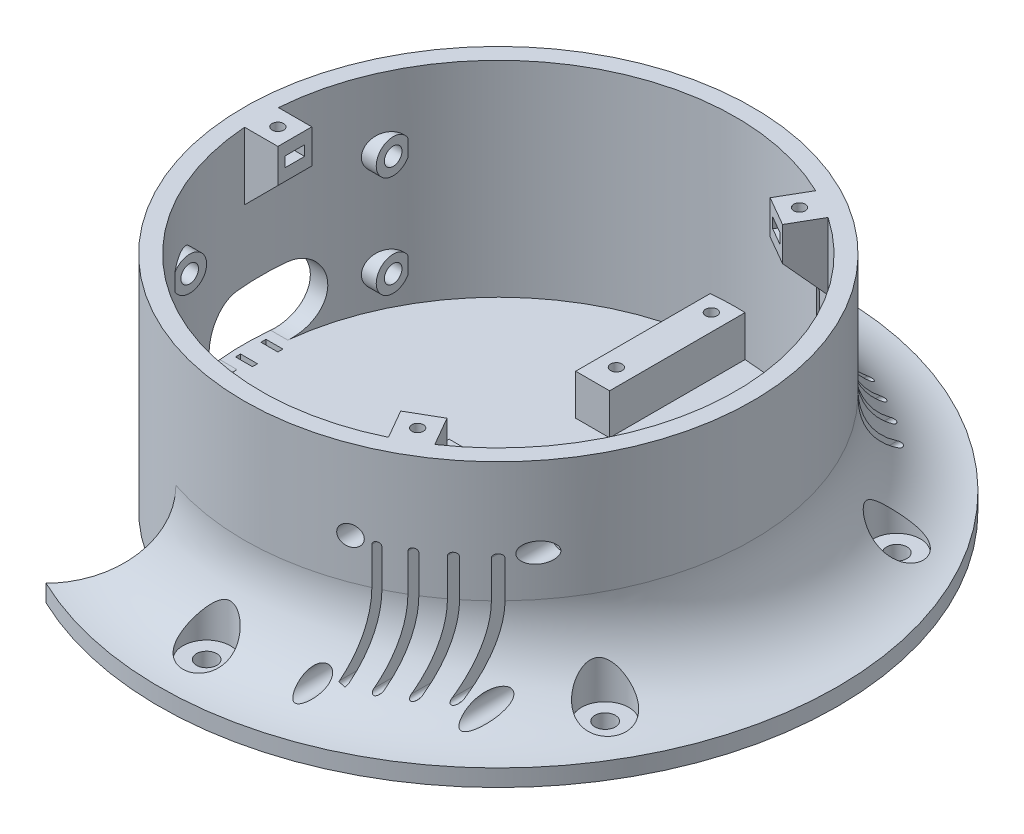
SolidWorks part; units mm, degrees
material "PLA"
ref_plane "Alzado" through (0, 0, 0) normal (0, 0, 1) x (1, 0, 0)
ref_plane "Planta" through (0, 0, 0) normal (0, 1, 0) x (1, 0, 0)
ref_plane "Vista lateral" through (0, 0, 0) normal (1, 0, 0) x (0, 0, -1)
sketch "Croquis1" plane through (0, 0, 0) normal (0, 0, 1) x (1, 0, 0)
  line L0 (0, 5) -> (0, 0)
  line L1 (0, 0) -> (100, 0)
  line L2 (100, 0) -> (100, 5)
  line L5 (75, 65.5) -> (70, 65.5)
  line L6 (70, 65.5) -> (70, 5)
  line L7 (70, 5) -> (0, 5)
  line L8 (0, 78.0387) -> (0, -48.9412) construction
  line L9 (75, 65.5) -> (75, 30)
  arc A0 (75, 30) -> (100, 5) centre (100, 30) ccw
  point P11 (100, 2.5)
  dimension "D6" = 50
  dimension "D1" = 65.5
  dimension "D2" = 70
  dimension "D3" = 75
  dimension "D4" = 100
  dimension "D5" = 5
  dimension "D7" = 5
  dimension "D8" = 35.5
revolve "Revolución1" add sketch "Croquis1" angle 360 about L8
sketch "Croquis2" plane through (0, 65.5, 0) normal (0, 1, 0) x (1, 0, 0)
  line L0 (-112.9437, 100) -> (-112.9437, -100)
  line L1 (-112.9437, 100) -> (-52.9437, 100)
  line L2 (-52.9437, 100) -> (-24, 71.0563)
  line L3 (-112.9437, -100) -> (-52.9437, -100)
  line L4 (-52.9437, -100) -> (-24, -71.0563)
  arc A0 (-24, 71.0563) -> (-24, -71.0563) centre (0, 0) ccw
  circle A1 centre (0, 0) radius 75 construction
  point P5 (-112.9437, 0)
  dimension "D1" = 200
  dimension "D2" = 60
  dimension "D3" = 135
  dimension "D4" = 24
extrude "Cortar-Extruir1" cut sketch "Croquis2" against normal blind 109
sketch "Croquis3" plane through (0, 0, 0) normal (0, 0, 1) x (1, 0, 0)
  line L0 (-72, 65.5) -> (-72, 43.5)
  line L2 (-72, 43.5) -> (-60, 55.5)
  line L3 (-60, 55.5) -> (-60, 65.5)
  line L4 (75, 65.5) -> (-75, 65.5) construction
  line L6 (-60, 65.5) -> (-70, 65.5)
  line L7 (-70, 65.5) -> (-72, 65.5)
  dimension "D1" = 10
  dimension "D2" = 45
  dimension "D3" = 10
  dimension "D4" = 2
  dimension "D5" = 70
extrude "Saliente-Extruir1" add sketch "Croquis3" along normal blind 5 and the other way blind 5
sketch "Croquis4" plane through (0, 65.5, 0) normal (0, 1, 0) x (1, 0, 0)
  line L0 (-60, 5) -> (-60, -5) construction
  circle A0 centre (-65, 0) radius 1.7
  point P6 (-60, 0)
  dimension "D2" = 3.4
  dimension "D1" = 5
extrude "Cortar-Extruir2" cut sketch "Croquis4" against normal blind 22
ref_plane "Plano1" through (0, 60.5, 0) normal (0, 1, 0) x (1, 0, 0)
sketch "Croquis5" plane through (0, 60.5, 0) normal (0, 1, 0) x (1, 0, 0)
  line L0 (-63.325, 2.9012) -> (-56.675, 2.9012)
  line L1 (-68.35, 0) -> (-66.675, -2.9012)
  line L2 (-66.675, -2.9012) -> (-63.325, -2.9012)
  line L5 (-63.325, 2.9012) -> (-66.675, 2.9012)
  line L6 (-66.675, 2.9012) -> (-68.35, 0)
  line L7 (-56.675, 2.9012) -> (-56.675, -2.9012)
  line L8 (-56.675, -2.9012) -> (-63.325, -2.9012)
  line L9 (-60, 5) -> (-69.8212, 5) construction
  line L10 (-61.65, 0) -> (-63.325, 2.9012) [skipped]
  line L11 (-62.4528, -1.3904) -> (-61.65, 0) [skipped]
  circle A0 centre (-65, 0) radius 3.35 construction
  dimension "D1" = 6.7
  dimension "D2" = 10
extrude "Cortar-Extruir3" cut sketch "Croquis5" against normal blind 1.5 and the other way blind 1.5
pattern_circular "MatrizC1" count 3 over 360 about axis through (0, 65.5, 0) along (0, 1, 0) of "Saliente-Extruir1", "Cortar-Extruir2", "Cortar-Extruir3"
sketch "Croquis6" plane through (0, 0, 0) normal (0, -1, 0) x (1, 0, 0)
  circle A0 centre (0, -86) radius 3
  dimension "D1" = 6
  dimension "D2" = 86
extrude "Cortar-Extruir4" cut sketch "Croquis6" against normal blind 30.35
ref_plane "Plano2" through (0, 20, 0) normal (0, -1, 0) x (-1, 0, 0)
sketch "Croquis7" plane through (0, 20, 0) normal (0, -1, 0) x (-1, 0, 0)
  circle A0 centre (0, 86) radius 7
  dimension "D1" = 14
extrude "Cortar-Extruir5" cut sketch "Croquis7" along normal blind 15
pattern_circular "MatrizC2" count 6 over 360 of "Cortar-Extruir4", "Cortar-Extruir5"
sketch "Croquis8" plane through (0, 0, 0) normal (0, -1, 0) x (1, 0, 0)
  line L1 (24.5, -15.5) -> (55.5, -15.5) construction
  line L2 (24.5, -15.5) -> (24.5, 15.5) construction
  line L3 (24.5, 15.5) -> (55.5, 15.5) construction
  line L4 (55.5, -15.5) -> (55.5, 15.5) construction
  circle A0 centre (24.5, 15.5) radius 1.7
  circle A1 centre (55.5, 15.5) radius 1.7
  circle A2 centre (24.5, -15.5) radius 1.7
  circle A3 centre (55.5, -15.5) radius 1.7
  point P4 (24.5, 0)
  dimension "D4" = 3.4
  dimension "D1" = 31
  dimension "D2" = 31
  dimension "D3" = 24.5
extrude "Cortar-Extruir6" cut sketch "Croquis8" against normal blind 15
sketch "Croquis9" plane through (0, 0, 0) normal (0, -1, 0) x (1, 0, 0)
  circle A0 centre (24.5, 15.5) radius 2.95
  circle A1 centre (24.5, -15.5) radius 2.95
  circle A2 centre (55.5, -15.5) radius 2.95
  circle A3 centre (55.5, 15.5) radius 2.95
  dimension "D1" = 5.9
extrude "Cortar-Extruir7" cut sketch "Croquis9" against normal blind 2.5
sketch "Croquis10" plane through (0, 5, 0) normal (0, 1, 0) x (1, 0, 0)
  line L1 (2.8, 30) -> (-7.2, 30)
  line L2 (2.8, 30) -> (2.8, 69.944)
  line L4 (-7.2, 30) -> (-7.2, 69.6287)
  arc A0 (2.8, 69.944) -> (-7.2, 69.6287) centre (0, 0) ccw
  circle A1 centre (0, 0) radius 70 construction
  dimension "D1" = 30
  dimension "D2" = 2.8
  dimension "D3" = 10
extrude "Saliente-Extruir2" add sketch "Croquis10" along normal blind 12
sketch "Croquis11" plane through (0, 17, 0) normal (0, 1, 0) x (1, 0, 0)
  circle A0 centre (-2.2, 37) radius 1.7
  dimension "D3" = 3.4
  dimension "D1" = 5
  dimension "D2" = 7
extrude "Cortar-Extruir8" cut sketch "Croquis11" against normal blind 21
ref_plane "Plano3" through (0, 10.65, 0) normal (0, 1, 0) x (1, 0, 0)
sketch "Croquis12" plane through (0, 10.65, 0) normal (0, 1, 0) x (1, 0, 0)
  line L0 (-3.875, 39.9012) -> (-10.525, 39.9012)
  line L2 (-3.875, 34.0988) -> (-0.525, 34.0988)
  line L3 (-0.525, 34.0988) -> (1.15, 37)
  line L4 (1.15, 37) -> (-0.525, 39.9012)
  line L5 (-0.525, 39.9012) -> (-3.875, 39.9012)
  line L7 (-10.525, 39.9012) -> (-10.525, 34.0988)
  line L8 (-10.525, 34.0988) -> (-3.875, 34.0988)
  line L9 (-7.2, 30) -> (2.8, 30) construction
  line L10 (-5.55, 37) -> (-3.875, 34.0988) [skipped]
  line L11 (-3.875, 39.9012) -> (-5.55, 37) [skipped]
  line L12 (-7.2, 30) -> (2.8, 30) construction
  circle A0 centre (-2.2, 37) radius 3.35 construction
  dimension "D1" = 6.7
  dimension "D2" = 10
extrude "Cortar-Extruir9" cut sketch "Croquis12" against normal blind 3
pattern_linear "MatrizL1" count 2 spacing 28 along (0, 0, -1) of "Cortar-Extruir8", "Cortar-Extruir9"
sketch "Croquis13" plane through (0, 5, 0) normal (0, 1, 0) x (1, 0, 0)
  line L1 (63.5, -36) -> (21.5, -36)
  line L2 (63.5, -36) -> (63.5, -26)
  line L3 (63.5, -26) -> (21.5, -26)
  line L4 (21.5, -36) -> (21.5, -26)
  dimension "D1" = 10
  dimension "D2" = 42
  dimension "D3" = 36
  dimension "D4" = 21.5
extrude "Cortar-Extruir10" cut sketch "Croquis13" along normal blind 42
sketch "Croquis14" plane through (0, 5, 0) normal (0, 1, 0) x (1, 0, 0)
  line L0 (60.0333, -36) -> (21.5, -36)
  line L1 (21.5, -36) -> (21.5, -66.6164)
  circle A0 centre (0, 0) radius 70
  arc A1 (39.2407, -57.9669) -> (39.2407, 57.9669) centre (0, 0) ccw construction
  arc A2 (-7.2, 69.6287) -> (60.0333, -36) centre (0, 0) ccw construction
  arc M4 (-7.2, 69.6287) -> (60.0333, -36) centre (0, 0) ccw
  dimension "D1" = 42
extrude "Saliente-Extruir3" add sketch "Croquis14" along normal blind 42 contours L0 L1 M4 region at (35.8526, 5, 47.5073)
sketch "Croquis15" plane through (0, 0, 36) normal (0, 0, -1) x (-1, 0, 0)
  line L0 (-53, 41) -> (-53, 11) construction
  line L1 (-32, 11) -> (-53, 11) construction
  line L2 (-32, 11) -> (-32, 41) construction
  line L3 (-32, 41) -> (-53, 41) construction
  line L4 (-53, 11) -> (-53, 41) construction
  line L5 (-32, 11) -> (-53, 41) construction
  line L6 (-32, 41) -> (-53, 11) construction
  line L7 (-52, 41) -> (-52, 11)
  line L8 (-54, 41) -> (-54, 11)
  line L9 (-32, 41) -> (-32, 11) construction
  line L10 (-31, 41) -> (-31, 11)
  line L11 (-33, 41) -> (-33, 11)
  line L12 (-46, 41) -> (-46, 11) construction
  line L13 (-45, 41) -> (-45, 11)
  line L14 (-47, 41) -> (-47, 11)
  line L15 (-39, 41) -> (-39, 11) construction
  line L16 (-38, 41) -> (-38, 11)
  line L17 (-40, 41) -> (-40, 11)
  arc A0 (-52, 41) -> (-54, 41) centre (-53, 41) ccw
  arc A1 (-54, 11) -> (-52, 11) centre (-53, 11) ccw
  arc A2 (-31, 41) -> (-33, 41) centre (-32, 41) ccw
  arc A3 (-33, 11) -> (-31, 11) centre (-32, 11) ccw
  arc A4 (-45, 41) -> (-47, 41) centre (-46, 41) ccw
  arc A5 (-47, 11) -> (-45, 11) centre (-46, 11) ccw
  arc A6 (-38, 41) -> (-40, 41) centre (-39, 41) ccw
  arc A7 (-40, 11) -> (-38, 11) centre (-39, 11) ccw
  point P0 (-42.5, 26)
  point P5 (-53, 26)
  point P12 (-32, 26)
  point P17 (-46, 26)
  point P24 (-39, 26)
  dimension "D7" = 1
  dimension "D1" = 30
  dimension "D2" = 7
  dimension "D3" = 21
  dimension "D4" = 21
  dimension "D5" = 7
  dimension "D6" = 7
extrude "Cortar-Extruir11" cut sketch "Croquis15" against normal blind 42 and the other way blind 129
sketch "Croquis16" plane through (0, 0, 36) normal (0, 0, -1) x (-1, 0, 0)
  line L7 (-26.5, 10) -> (-58.5, 10) construction
  line L8 (-26.5, 10) -> (-26.5, 42) construction
  line L9 (-26.5, 42) -> (-58.5, 42) construction
  line L10 (-58.5, 10) -> (-58.5, 42) construction
  line L11 (-26.5, 10) -> (-58.5, 42) construction
  line L12 (-26.5, 42) -> (-58.5, 10) construction
  circle A0 centre (-58.5, 42) radius 1.7
  circle A1 centre (-26.5, 42) radius 1.7
  circle A2 centre (-58.5, 10) radius 1.7
  circle A3 centre (-26.5, 10) radius 1.7
  point P5 (-42.5, 26)
  dimension "D5" = 3.4
  dimension "D1" = 21
  dimension "D2" = 21
  dimension "D3" = 32
  dimension "D4" = 32
extrude "Cortar-Extruir12" cut sketch "Croquis16" against normal blind 67
ref_plane "Plano4" through (0, 0, 101) normal (0, 0, -1) x (-1, 0, 0)
sketch "Croquis17" plane through (0, 0, 101) normal (0, 0, -1) x (-1, 0, 0)
  circle A0 centre (-26.5, 42) radius 2.95
  circle A1 centre (-26.5, 10) radius 2.95
  dimension "D1" = 5.9
extrude "Cortar-Extruir13" cut sketch "Croquis17" along normal blind 37
sketch "Croquis18" plane through (0, 0, 101) normal (0, 0, -1) x (-1, 0, 0)
  circle A0 centre (-58.5, 42) radius 2.95
  circle A1 centre (-58.5, 10) radius 2.95
  dimension "D1" = 5.9
extrude "Cortar-Extruir14" cut sketch "Croquis18" along normal blind 61
sketch "Croquis19" plane through (0, 0, 0) normal (1, 0, 0) x (0, 0, -1)
  line L0 (7.5, 15) -> (-7.5, 15) construction
  line L1 (7.5, 5) -> (-7.5, 5)
  line L2 (7.5, 25) -> (-7.5, 25)
  line L3 (-100, 0) -> (100, 0) construction
  arc A0 (7.5, 5) -> (7.5, 25) centre (7.5, 15) ccw
  arc A1 (-7.5, 25) -> (-7.5, 5) centre (-7.5, 15) ccw
  point P2 (0, 15)
  dimension "D2" = 10
  dimension "D1" = 15
  dimension "D3" = 5
extrude "Cortar-Extruir15" cut sketch "Croquis19" against normal blind 105
sketch "Croquis21" plane through (0, 5, 0) normal (0, 1, 0) x (1, 0, 0)
  line L1 (-73, 4.5) -> (-68, 4.5)
  line L2 (-73, 4.5) -> (-73, 3)
  line L3 (-73, 3) -> (-68, 3)
  line L4 (-68, 4.5) -> (-68, 3)
  line L5 (-73, 4.5) -> (-68, 3) construction
  line L6 (-73, 3) -> (-68, 4.5) construction
  line L7 (-73, -3) -> (-68, -3)
  line L8 (-73, -3) -> (-73, -4.5)
  line L9 (-73, -4.5) -> (-68, -4.5)
  line L10 (-68, -3) -> (-68, -4.5)
  line L11 (-73, -3) -> (-68, -4.5) construction
  line L12 (-73, -4.5) -> (-68, -3) construction
  point P0 (-70.5, 3.75)
  point P5 (-70.5, -3.75)
  dimension "D1" = 6
  dimension "D2" = 3
  dimension "D3" = 1.5
  dimension "D4" = 5
  dimension "D5" = 68
ref_plane "Plano6" through (-75, 0, 0) normal (-1, 0, 0) x (0, 0, 1)
sketch "Croquis22" plane through (-75, 0, 0) normal (-1, 0, 0) x (0, 0, 1)
  line L1 (30, 15) -> (-30, 15) construction
  line L2 (30, 15) -> (30, 45) construction
  line L3 (30, 45) -> (-30, 45) construction
  line L4 (-30, 15) -> (-30, 45) construction
  line L5 (30, 15) -> (-30, 45) construction
  line L6 (30, 45) -> (-30, 15) construction
  line L7 (-71.0563, 0) -> (71.0563, 0) construction
  circle A0 centre (-30, 45) radius 2.6
  circle A1 centre (-30, 15) radius 2.6
  circle A2 centre (30, 15) radius 2.6
  circle A3 centre (30, 45) radius 2.6
  point P0 (0, 30)
  point P10 (0, 0)
  dimension "D3" = 5.2
  dimension "D1" = 60
  dimension "D2" = 30
  dimension "D4" = 30
extrude "Cortar-Extruir16" cut sketch "Croquis22" against normal blind 14
ref_plane "Plano7" through (-61, 0, 0) normal (1, 0, 0) x (0, 0, -1)
sketch "Croquis23" plane through (-61, 0, 0) normal (1, 0, 0) x (0, 0, -1)
  circle A0 centre (-30, 45) radius 5
  circle A1 centre (-30, 15) radius 5
  circle A2 centre (30, 15) radius 5
  circle A3 centre (30, 45) radius 5
  circle A4 centre (30, 45) radius 2.6 construction
  circle A5 centre (30, 15) radius 2.6 construction
  circle A6 centre (-30, 15) radius 2.6 construction
  circle A7 centre (-30, 45) radius 2.6 construction
  circle A8 centre (30, 45) radius 2.6
  circle A9 centre (30, 15) radius 2.6
  circle A10 centre (-30, 15) radius 2.6
  circle A11 centre (-30, 45) radius 2.6
  dimension "D1" = 10
extrude "Saliente-Extruir4" add sketch "Croquis23" against normal up to surface (4.3835 mm away) up to face at (-61.9829, 44.3955, -32.5287)
extrude "Cortar-Extruir17" cut sketch "Croquis21" against normal blind 18
